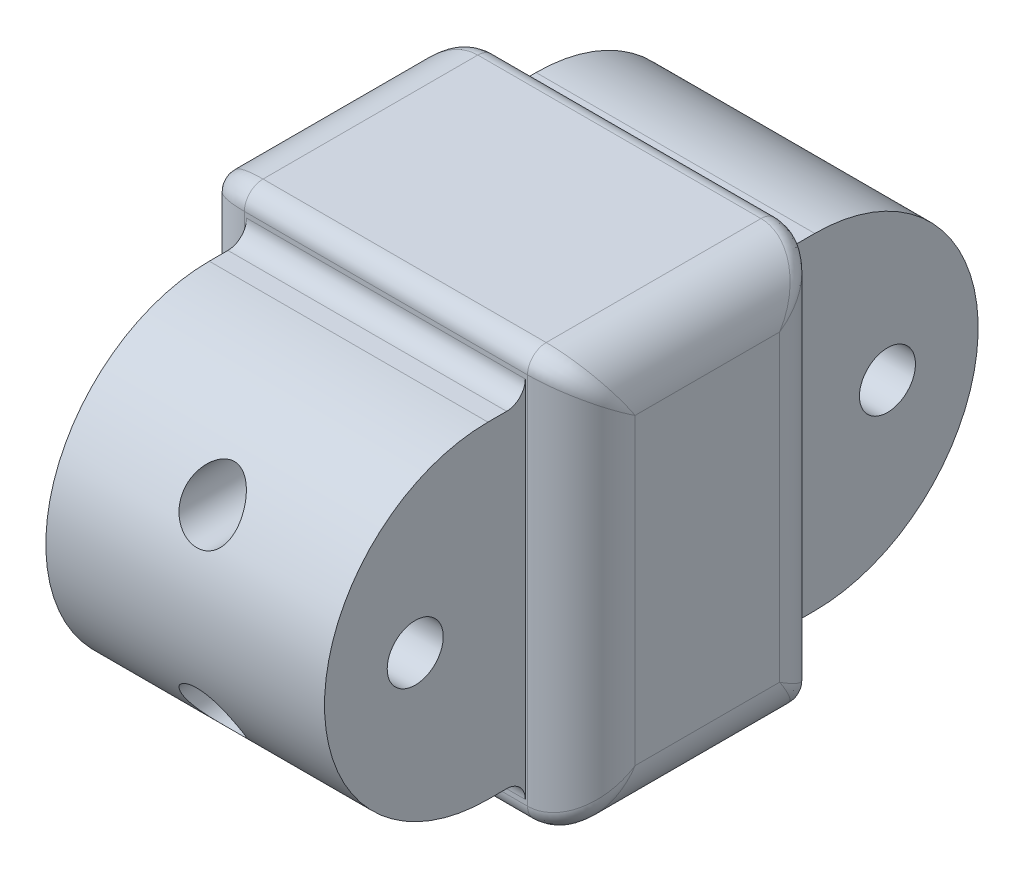
SolidWorks part; units mm, degrees
ref_plane "Front Plane" through (0, 0, 0) normal (0, 0, 1) x (1, 0, 0)
ref_plane "Top Plane" through (0, 0, 0) normal (0, 1, 0) x (1, 0, 0)
ref_plane "Right Plane" through (0, 0, 0) normal (1, 0, 0) x (0, 0, -1)
sketch3d "3DSketch1"
  line L2 (-19.9456, 27.4792, 53.8354) -> (0.9768, 27.4792, 53.8354)
  line L4 (-19.9456, 27.4792, 53.8354) -> (-19.9456, 5.4792, 53.8354)
  line L5 (-19.9456, 5.4792, 53.8354) -> (0.9768, 5.4792, 53.8354)
  line L6 (0.9768, 5.4792, 53.8354) -> (0.9768, 27.4792, 53.8354)
ref_plane "Plane1" through (0, 0, 53.8354) normal (0, 0, -1) x (-1, 0, 0)
sketch "Sketch2" plane through (0, 0, 53.8354) normal (0, 0, -1) x (-1, 0, 0)
  line L0 (19.9456, 27.4792) -> (19.9456, 5.4792)
  line L1 (19.9456, 5.4792) -> (-0.9768, 5.4792)
  line L2 (-0.9768, 5.4792) -> (-0.9768, 27.4792)
  line L3 (-0.9768, 27.4792) -> (19.9456, 27.4792)
extrude "Boss-Extrude1" add sketch "Sketch2" against normal blind 35
sketch "Sketch3" plane through (-19.9456, 0, 0) normal (-1, 0, 0) x (0, 0, 1)
  line L1 (88.8354, 27.4792) -> (53.8354, 27.4792) construction
  line L2 (88.8354, 5.4792) -> (53.8354, 5.4792) construction
  line L4 (88.8354, 5.4792) -> (88.8354, 27.4792) construction
  line L9 (71.3354, 27.4792) -> (71.3354, 5.4792) construction
  line L10 (62.5854, 25.2292) -> (62.5854, 27.4792)
  line L11 (62.5854, 7.7292) -> (62.5854, 5.4792)
  line L12 (53.8354, 16.4792) -> (58.6921, 16.4792) construction
  line L13 (80.0854, 27.4792) -> (80.0854, 16.4792) construction
  line L15 (71.3354, 27.4792) -> (71.3354, 5.4792) construction
  line L16 (71.3354, 5.4792) -> (88.8354, 5.4792) construction
  line L17 (88.8354, 27.4792) -> (88.8354, 5.4792) construction
  line L19 (80.0854, 25.2292) -> (80.0854, 27.4792)
  line L20 (80.0854, 7.7292) -> (80.0854, 5.4792)
  arc A1 (53.8354, 16.4792) -> (62.5854, 25.2292) centre (62.5854, 16.4792) cw
  arc A2 (53.8354, 16.4792) -> (62.5854, 7.7292) centre (62.5854, 16.4792) ccw
  circle A3 centre (58.6921, 16.4792) radius 1.5
  arc A4 (88.8354, 16.4792) -> (80.0854, 7.7292) centre (80.0854, 16.4792) cw
  arc A5 (88.8354, 16.4792) -> (80.0854, 25.2292) centre (80.0854, 16.4792) ccw
  circle A6 centre (83.9786, 16.4792) radius 1.5
  spline S0 degree 3 poles (62.5854, 5.4792) (55.5032, -7.5997) (27.6429, 16.7569) (54.8472, 35.9656) (62.5854, 27.4792) knots 0 0 0 0 0.523232 1 1 1 1
  spline S1 degree 3 poles (80.0854, 5.4792) (87.4399, -7.3101) (114.9239, 16.4819) (87.4008, 40.475) (80.0854, 27.4792) knots 0 0 0 0 0.498892 1 1 1 1
extrude "Cut-Extrude1" cut sketch "Sketch3" against normal blind 31
sketch "Sketch4" plane through (0.9768, 0, 0) normal (1, 0, 0) x (0, 0, -1)
  line L0 (-53.8354, 16.4792) -> (-58.6921, 16.4792)
  line L1 (-53.8354, 5.4792) -> (-53.8354, 27.4792) construction
sketch "Sketch7" plane through (-19.9456, 0, 0) normal (-1, 0, 0) x (0, 0, 1)
  line L0 (62.5854, 25.2292) -> (64.5854, 25.2292)
  line L1 (64.5854, 25.2292) -> (64.5854, 27.4792)
  line L2 (80.0854, 27.4792) -> (62.5854, 27.4792) construction
  line L3 (64.5854, 27.4792) -> (62.5854, 27.4792)
  line L4 (62.5854, 27.4792) -> (62.5854, 25.2292)
  line L5 (80.0854, 25.2292) -> (78.0854, 25.2292)
  line L6 (78.0854, 25.2292) -> (78.0854, 27.4792)
  line L7 (78.0854, 27.4792) -> (80.0854, 27.4792)
  line L8 (80.0854, 27.4792) -> (80.0854, 25.2292)
extrude "Cut-Extrude3" cut sketch "Sketch7" against normal blind 22
sketch "Sketch8" plane through (-19.9456, 0, 0) normal (-1, 0, 0) x (0, 0, 1)
  line L0 (62.5854, 5.4792) -> (64.5854, 5.4792)
  line L1 (80.0854, 5.4792) -> (62.5854, 5.4792) construction
  line L2 (62.5854, 5.4792) -> (62.5854, 7.7292)
  line L3 (62.5854, 7.7292) -> (64.5854, 7.7292)
  line L4 (64.5854, 7.7292) -> (64.5854, 5.4792)
  line L5 (78.0854, 5.4792) -> (80.0854, 5.4792)
  line L6 (80.0854, 5.4792) -> (80.0854, 7.7292)
  line L7 (80.0854, 7.7292) -> (78.0854, 7.7292)
  line L8 (78.0854, 7.7292) -> (78.0854, 5.4792)
extrude "Cut-Extrude4" cut sketch "Sketch8" against normal blind 22
ref_plane "Plane8" through (-19.9456, 25.2292, 64.5854) normal (0, 1, 0) x (1, 0, 0)
sketch "Sketch11" plane through (0, 0, 53.8354) normal (0, 0, -1) x (-1, 0, 0)
  line L0 (19.9456, 5.4792) -> (19.9456, 7.7292) construction
  line L1 (19.9456, 27.4792) -> (19.9456, 5.4792) construction
  line L2 (9.4844, 22.7342) -> (9.4844, 27.4792) construction
  line L3 (-0.9768, 5.4792) -> (-0.9768, 27.4792) construction
  line L4 (-0.9768, 7.7292) -> (-0.9768, 5.4792) construction
  line L5 (19.9456, 27.4792) -> (19.9456, 25.2292) construction
  line L6 (19.9456, 27.4792) -> (-0.9768, 27.4792) construction
  line L7 (-0.9768, 25.2292) -> (-0.9768, 27.4792) construction
  line L8 (19.9456, 7.7292) -> (19.9456, 11.7292) construction
  line L9 (9.4844, 27.4792) -> (9.4844, 21.2342) construction
  line L11 (19.9456, 25.2292) -> (19.9456, 21.2342) construction
  line L13 (19.9456, 25.2292) -> (16.9456, 25.2292) construction
  line L14 (16.9456, 25.2292) -> (16.9456, 22.2292) construction
  line L15 (19.9456, 7.7292) -> (16.9456, 7.7292) construction
  line L16 (16.9456, 7.7292) -> (16.9456, 10.7292) construction
  line L17 (-0.9768, 7.7292) -> (2.0232, 7.7292) construction
  line L18 (2.0232, 7.7292) -> (2.0232, 10.7292) construction
  line L19 (-0.9768, 25.2292) -> (2.0232, 25.2292) construction
  line L20 (2.0232, 25.2292) -> (2.0232, 22.2292) construction
  line L22 (-0.9768, 25.2292) -> (2.0232, 25.2292)
  line L23 (-0.9768, 25.2292) -> (-0.9768, 7.7292)
  line L24 (-0.9768, 7.7292) -> (2.0232, 7.7292)
  line L25 (2.0232, 25.2292) -> (2.0232, 7.7292)
  line L26 (16.9456, 25.2292) -> (19.9456, 25.2292)
  line L27 (16.9456, 25.2292) -> (16.9456, 7.7292)
  line L28 (16.9456, 7.7292) -> (19.9456, 7.7292)
  line L29 (19.9456, 25.2292) -> (19.9456, 7.7292)
  circle A0 centre (9.4844, 11.7292) radius 1.5
  circle A1 centre (9.4844, 21.2342) radius 1.5
extrude "Cut-Extrude5" cut sketch "Sketch11" against normal blind 36
fillet "Fillet2" radius 1 8 edges at (-9.4844, 25.2292, 78.0854) (-9.4844, 27.4792, 78.0854) (-9.4844, 27.4792, 64.5854) (-9.4844, 25.2292, 64.5854) (-9.4844, 7.7292, 64.5854) (-9.4844, 5.4792, 64.5854) (-9.4844, 5.4792, 78.0854) (-9.4844, 7.7292, 78.0854)
sketch "Sketch14" plane through (0, 25.2292, 0) normal (0, -1, 0) x (1, 0, 0)
  line L1 (0.9768, 78.0854) -> (-2.0232, 78.0854)
  line L2 (0.9768, 78.0854) -> (0.9768, 64.5854)
  line L3 (0.9768, 64.5854) -> (-2.0232, 64.5854)
  line L4 (-2.0232, 78.0854) -> (-2.0232, 64.5854)
  line L5 (-16.9456, 64.5854) -> (-19.9456, 64.5854)
  line L6 (-16.9456, 64.5854) -> (-16.9456, 78.0854)
  line L7 (-16.9456, 78.0854) -> (-19.9456, 78.0854)
  line L8 (-19.9456, 64.5854) -> (-19.9456, 78.0854)
extrude "Boss-Extrude2" add sketch "Sketch14" along normal up to surface (17.5 mm away) up to face at (-18.4456, 7.7292, 71.3354)
fillet "Fillet3" radius 2.88 16 edges at (0.9768, 27.1863, 64.8782) (0.9768, 16.4792, 64.5854) (0.9768, 5.7721, 64.8782) (0.9768, 5.4792, 71.3354) (0.9768, 5.7721, 77.7925) (0.9768, 16.4792, 78.0854) (0.9768, 27.1863, 77.7925) (0.9768, 27.4792, 71.3354) (-19.9456, 5.7721, 77.7925) (-19.9456, 5.4792, 71.3354) (-19.9456, 5.7721, 64.8782) (-19.9456, 16.4792, 64.5854) (-19.9456, 27.1863, 64.8782) (-19.9456, 27.4792, 71.3354) (-19.9456, 27.1863, 77.7925) (-19.9456, 16.4792, 78.0854)
